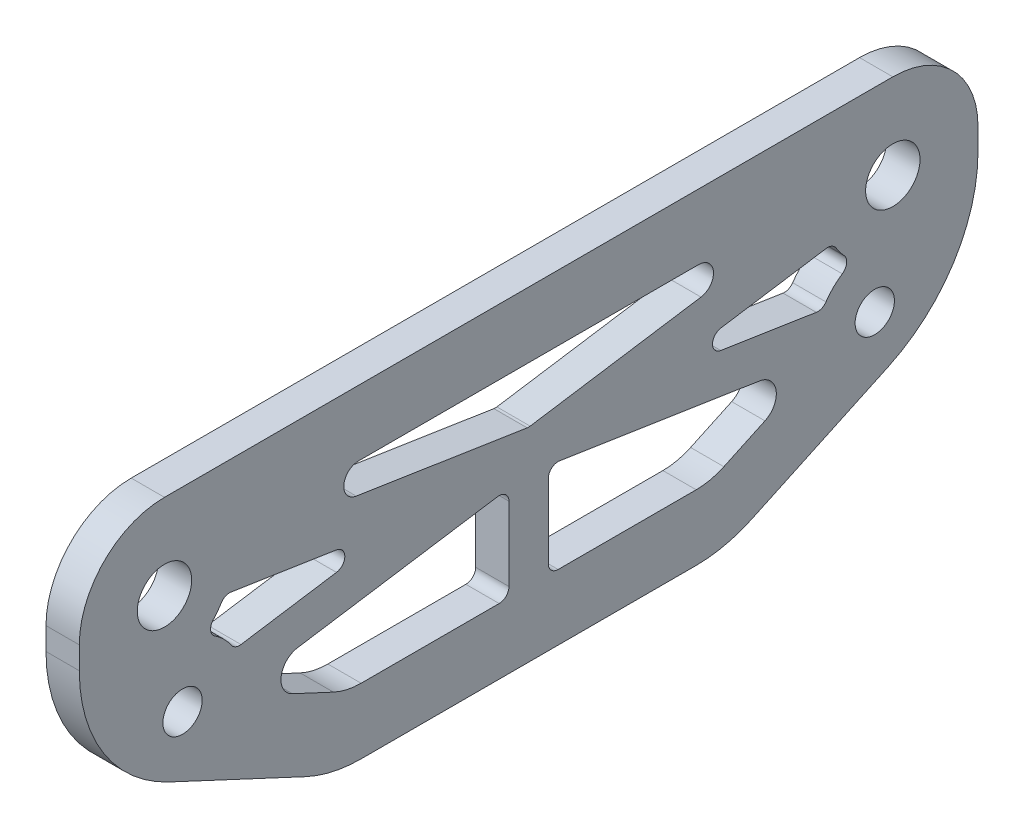
SolidWorks part; units mm, degrees
ref_plane "Front Plane" through (0, 0, 0) normal (0, 0, 1) x (1, 0, 0)
ref_plane "Top Plane" through (0, 0, 0) normal (0, 1, 0) x (1, 0, 0)
ref_plane "Right Plane" through (0, 0, 0) normal (1, 0, 0) x (0, 0, -1)
sketch "Sketch1" plane through (0, 0, 0) normal (1, 0, 0) x (0, 0, -1)
  line L0 (15, 12.3931) -> (27.786, 12.3931)
  line L1 (-15, -12.3931) -> (15, -12.3931)
  line L3 (-15, 12.3931) -> (15, 12.3931)
  line L5 (-15, -12.3931) -> (15, 12.3931) construction
  line L6 (-15, 12.3931) -> (15, -12.3931) construction
  line L8 (0, 12.3931) -> (0, -12.3931) construction
  line L10 (-15, 12.3931) -> (-27.786, 12.3931)
  line L11 (22.286, 82.4266) -> (22.286, -144.9734) construction
  line L13 (34.286, 5.8931) -> (34.286, 4.1845)
  line L14 (27.4122, -6.6052) -> (15, -12.3931)
  line L16 (-34.286, 5.8931) -> (-34.286, 4.1845)
  line L17 (-27.4122, -6.6052) -> (-15, -12.3931)
  arc A0 (27.786, 12.3931) -> (34.286, 5.8931) centre (27.786, 5.8931) cw
  circle A1 centre (27.786, 5.8931) radius 5.5 construction
  circle A2 centre (-27.786, 5.8931) radius 5.5 construction
  arc A3 (-27.786, 12.3931) -> (-34.286, 5.8931) centre (-27.786, 5.8931) ccw
  arc A4 (34.286, 4.1845) -> (27.4122, -6.6052) centre (22.3809, 4.1845) cw
  circle A5 centre (27.786, 5.8931) radius 2.075
  arc A6 (-34.286, 4.1845) -> (-27.4122, -6.6052) centre (-22.3809, 4.1845) ccw
  circle A9 centre (-27.786, 5.8931) radius 2.075
  circle A11 centre (26.4083, -2.4557) radius 1.5
  circle A12 centre (-26.4083, -2.4557) radius 1.5
  point P0 (0, 0)
  point P24 (26.4083, -2.4557)
  point P28 (0, 0)
  dimension "D1" = 11
  dimension "D2" = 1
  dimension "D3" = 4.15
  dimension "D4" = 3
  dimension "D6" = 25
  dimension "D7" = 30
extrude "Boss-Extrude1" add sketch "Sketch1" along normal blind 2.54
fillet "Fillet1" radius 10 2 edges at (1.27, -12.3931, -15) (1.27, -12.3931, 15)
sketch "Sketch2" plane through (0, 0, 0) normal (1, 0, 0) x (0, 0, -1)
  line L0 (-27.786, 5.8931) -> (26.4083, -2.4557) construction
  line L10 (-27.786, -2.6679) -> (27.786, 5.8931)
  line L11 (-27.786, 5.8931) -> (26.4083, -2.4557)
  line L12 (-28.0144, 4.4106) -> (26.18, -3.9382)
  line L13 (-27.5576, 7.3756) -> (26.6367, -0.9731)
  line L14 (-28.0144, 4.4106) -> (-27.5576, 7.3756)
  line L15 (26.18, -3.9382) -> (26.6367, -0.9731)
  line L16 (-12.7831, -7.3931) -> (12.7831, -7.3931)
  line L17 (14.8961, -6.9246) -> (25.2991, -2.0737)
  line L18 (29.286, 4.1845) -> (29.286, 5.8931)
  line L19 (27.786, 7.3931) -> (-27.786, 7.3931)
  line L20 (-29.286, 5.8931) -> (-29.286, 4.1845)
  line L21 (-25.2991, -2.0737) -> (-14.8961, -6.9246)
  line L22 (-12.7831, -7.3931) -> (12.7831, -7.3931)
  line L23 (14.8961, -6.9246) -> (25.2991, -2.0737)
  line L24 (29.286, 4.1845) -> (29.286, 5.8931)
  line L25 (27.786, 7.3931) -> (-27.786, 7.3931)
  line L26 (-29.286, 5.8931) -> (-29.286, 4.1845)
  line L27 (-25.2991, -2.0737) -> (-14.8961, -6.9246)
  line L28 (-27.5576, -4.1504) -> (28.0144, 4.4106)
  line L29 (-28.0144, -1.1854) -> (27.5576, 7.3756)
  line L30 (-27.5576, -4.1504) -> (-28.0144, -1.1854)
  line L31 (28.0144, 4.4106) -> (27.5576, 7.3756)
  line L32 (0, -7.3931) -> (0, 7.3931) construction
  line L33 (0, 1.6126) -> (0, -7.3931)
  line L34 (-1.5, 1.6126) -> (-1.5, -7.3931)
  line L35 (1.5, 1.6126) -> (1.5, -7.3931)
  line L36 (-1.5, 1.6126) -> (1.5, 1.6126)
  line L37 (-1.5, -7.3931) -> (1.5, -7.3931)
  arc A0 (-17.6263, -2.6205) -> (-18.0318, -5.4624) centre (-17.3979, -4.103) ccw
  arc A1 (17.6263, -2.6205) -> (18.0318, -5.4624) centre (17.3979, -4.103) cw
  circle A2 centre (-26.4083, -2.4557) radius 4.5
  circle A3 centre (-26.4083, -2.4557) radius 4.5
  circle A5 centre (26.4083, -2.4557) radius 4.5
  circle A6 centre (26.4083, -2.4557) radius 4.5
  circle A11 centre (-27.786, 5.8931) radius 5.075
  arc A12 (12.7831, -7.3931) -> (14.8961, -6.9246) centre (12.7831, -2.3931) ccw
  arc A13 (25.2991, -2.0737) -> (29.286, 4.1845) centre (22.3809, 4.1845) ccw
  arc A14 (29.286, 5.8931) -> (27.786, 7.3931) centre (27.786, 5.8931) ccw
  arc A15 (-27.786, 7.3931) -> (-29.286, 5.8931) centre (-27.786, 5.8931) ccw
  arc A16 (-29.286, 4.1845) -> (-25.2991, -2.0737) centre (-22.3809, 4.1845) ccw
  arc A17 (-14.8961, -6.9246) -> (-12.7831, -7.3931) centre (-12.7831, -2.3931) ccw
  arc A18 (12.7831, -7.3931) -> (14.8961, -6.9246) centre (12.7831, -2.3931) ccw
  arc A19 (25.2991, -2.0737) -> (29.286, 4.1845) centre (22.3809, 4.1845) ccw
  arc A20 (29.286, 5.8931) -> (27.786, 7.3931) centre (27.786, 5.8931) ccw
  arc A21 (-27.786, 7.3931) -> (-29.286, 5.8931) centre (-27.786, 5.8931) ccw
  arc A22 (-29.286, 4.1845) -> (-25.2991, -2.0737) centre (-22.3809, 4.1845) ccw
  arc A23 (-14.8961, -6.9246) -> (-12.7831, -7.3931) centre (-12.7831, -2.3931) ccw
  circle A24 centre (-27.786, 5.8931) radius 5.075
  circle A26 centre (27.786, 5.8931) radius 5.075
  circle A27 centre (27.786, 5.8931) radius 5.075
  arc A32 (12.9795, 7.3931) -> (13.1508, 5.1562) centre (12.9795, 6.2681) cw
  arc A33 (-12.9795, 7.3931) -> (-13.1508, 5.1562) centre (-12.9795, 6.2681) ccw
  point P4 (-18.381, -4.1504)
  dimension "D11" = 3
  dimension "D12" = 1.125
  dimension "D2" = 1.5
  dimension "D1" = 5
  dimension "D3" = 3
  dimension "D4" = 3
  dimension "D6" = 1.5
  dimension "D7" = 1.5
  dimension "D8" = 1.5
  dimension "D9" = 1.5
  dimension "D13" = 1.5
  dimension "D14" = 1.5
  dimension "D15" = 3
extrude "Cut-Extrude2" cut sketch "Sketch2" along normal through all contours A24 A3 L29 L12 | A27 L28 L13 A6 | L25 A33 L13 L29 A32 | A1 L12 L35 L22 | L28 A0 L22 L34 region at (0, 1.6682, 19.033) region at (0, -4.2501, 9.0264) region at (0, 5.7355, 0) region at (0, -4.2501, -9.0264) region at (0, 1.6682, -19.033)
fillet "Fillet2" radius 0.75 13 edges at (1.27, -7.3931, -1.5) (1.27, 3.6724, -23.2226) (1.27, 1.6126, -9.8518) (1.27, 3.6724, 23.2226) (1.27, 3.1303, 0) (1.27, -0.1362, -1.5) (1.27, -7.3931, 1.5) (1.27, -0.1362, 1.5) (1.27, 1.6126, 9.8518) (1.27, -0.3272, -22.4435) (1.27, 1.7617, -24.8386) (1.27, -0.3272, 22.4435) (1.27, 1.7617, 24.8386)
